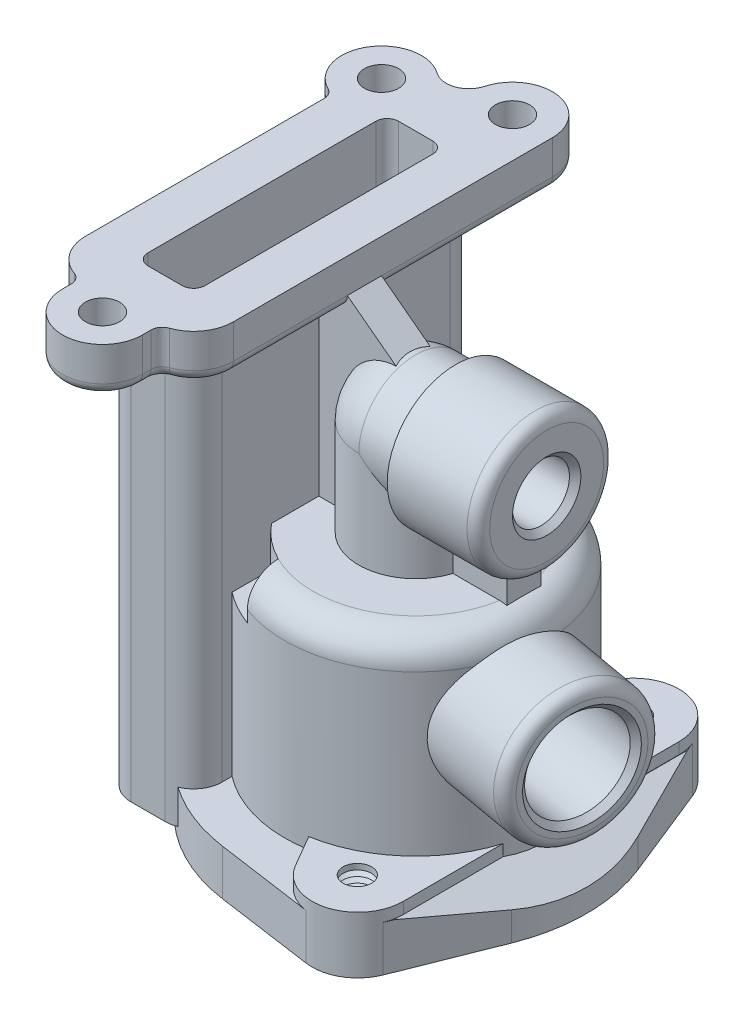
SolidWorks part; units mm, degrees
ref_plane "前基準面" through (0, 0, 0) normal (0, 0, 1) x (1, 0, 0)
ref_plane "上基準面" through (0, 0, 0) normal (0, 1, 0) x (1, 0, 0)
ref_plane "右基準面" through (0, 0, 0) normal (1, 0, 0) x (0, 0, -1)
sketch "草圖1" plane through (0, 0, 0) normal (0, 1, 0) x (1, 0, 0)
  line L0 (-34.2943, 4.8888) -> (-23.6038, 18.5165)
  line L1 (-34.277, -5.0086) -> (-23.539, -18.5989)
  line L2 (21.381, 27.2554) -> (27.8376, 11.1833)
  line L3 (12.8009, 32.1891) -> (-4.3376, 29.6848)
  line L4 (12.9133, -32.1441) -> (-4.2338, -29.6997)
  line L5 (21.4761, -27.1804) -> (27.8766, -11.0859)
  arc A0 (27.8766, -11.0859) -> (27.8376, 11.1833) centre (0, 0) ccw
  arc A1 (-34.2943, 4.8888) -> (-34.277, -5.0086) centre (-28, -0.0489) ccw
  arc A2 (21.381, 27.2554) -> (12.8009, 32.1891) centre (13.9576, 24.2731) ccw
  arc A3 (12.9133, -32.1441) -> (21.4761, -27.1804) centre (14.0424, -24.2242) ccw
  arc A4 (-4.3376, 29.6848) -> (-23.6038, 18.5165) centre (0, 0) ccw
  arc A5 (-23.539, -18.5989) -> (-4.2338, -29.6997) centre (0, 0) ccw
  dimension "D1" = 60
  dimension "D3" = 16
  dimension "D2" = 28
extrude "伸長1" add sketch "草圖1" along normal blind 8
sketch "草圖2" plane through (0, 0, 0) normal (0, 0, 1) x (1, 0, 0)
  line L0 (0, -12.2996) -> (0, 56.8744) construction
  line L1 (10, 60) -> (10, 43)
  line L2 (10, 43) -> (23, 43)
  line L3 (23, 43) -> (23, 0)
  line L4 (12.9133, 0) -> (21.4761, 0) construction
  line L5 (23, 0) -> (0, 0)
  line L6 (0, 0) -> (0, 70)
  arc A0 (10, 60) -> (0, 70) centre (0, 60) ccw
  dimension "D1" = 20
  dimension "D2" = 60
  dimension "D3" = 46
  dimension "D4" = 43
revolve "旋轉1" add sketch "草圖2" angle 360 about L0
sketch "草圖5" plane through (0, 8, 0) normal (0, 1, 0) x (-1, 0, 0)
  line L0 (-21.9576, -24.2731) -> (-22.0424, 24.2242)
  line L1 (-13.9576, -24.2731) -> (0, 0) construction
  line L2 (0, 0) -> (-14.0424, 24.2242) construction
  line L3 (-7.0224, -28.261) -> (9.2376, 0.0161)
  line L4 (9.2376, 0.0161) -> (-7.1212, 28.2363)
  arc A0 (-21.9576, -24.2731) -> (-7.0224, -28.261) centre (-13.9576, -24.2731) ccw
  arc A1 (-7.1212, 28.2363) -> (-22.0423, 24.1962) centre (-14.0424, 24.2242) ccw
  circle M1 centre (0, 0) radius 23
  arc M6 (-12.9133, 32.1441) -> (-21.4761, 27.1804) centre (-14.0424, 24.2242) ccw
  arc M10 (-21.381, -27.2554) -> (-12.8009, -32.1891) centre (-13.9576, -24.2731) ccw
extrude "伸長2" add sketch "草圖5" along normal blind 2 contours L3 L4 L0 M1 | L0 A0 L3 M10 M1 | A1 L0 L4 M6 M1
sketch "草圖6" plane through (0, 0, 0) normal (0, 0, 1) x (1, 0, 0)
  line L0 (22.0117, 8) -> (30, 4)
  line L1 (30, 0) -> (30, 8) construction
  line L2 (30, 4) -> (30, 8)
  line L3 (30, 8) -> (22.0117, 8)
  dimension "D1" = 4
extrude "除料-伸長2" cut sketch "草圖6" against normal through all and the other way through all
sketch "草圖7" plane through (0, 8, 0) normal (0, -1, 0) x (1, 0, 0)
  line L1 (22.0117, 6.6698) -> (22.0117, -6.6698)
  line L2 (22.0117, 6.6698) -> (22.0117, -6.6698)
  arc A1 (22.0117, -6.6698) -> (22.0117, 6.6698) centre (0, 0) ccw
  arc A2 (22.0117, -6.6698) -> (22.0117, 6.6698) centre (0, 0) ccw
  dimension "D1" = 0
extrude "伸長3" add sketch "草圖7" along normal up to next
sketch "草圖8" plane through (0, 0, 0) normal (0, 0, 1) x (1, 0, 0)
  line L0 (0, 60) -> (36.9487, 60) construction
  line L1 (10, 60) -> (-10, 60) construction
  line L2 (0, 60) -> (0, 70)
  line L3 (7, 60) -> (23, 60)
  line L4 (7, 70) -> (7, 72)
  line L5 (7, 72) -> (23, 72)
  line L6 (23, 60) -> (23, 72)
  line L7 (0, 70) -> (7, 70)
  line L8 (0, 60) -> (7, 60)
  arc A0 (10, 60) -> (-10, 60) centre (0, 60) ccw construction
  dimension "D1" = 16
  dimension "D2" = 24
  dimension "D3" = 23
revolve "旋轉2" add sketch "草圖8" angle 360 about L0
ref_plane "平面1" through (0, 28, 0) normal (0, 1, 0) x (-1, 0, 0)
sketch "草圖9" plane through (0, 28, 0) normal (0, 1, 0) x (-1, 0, 0)
  line L0 (0, 0) -> (-48.1518, 0) construction
  line L1 (0, 0) -> (-55.67, 9.8161) construction
  line L2 (-33.3693, 18.069) -> (-35.4531, 6.2513)
  line L3 (-35.4531, 6.2513) -> (0, 0)
  line L4 (0, 0) -> (2.0838, 11.8177)
  line L5 (-33.3693, 18.069) -> (2.0838, 11.8177)
  dimension "D1" = 10
  dimension "D2" = 36
  dimension "D3" = 24
revolve "旋轉3" add sketch "草圖9" angle 360 about L1
ref_plane "平面2" through (0, 82, 0) normal (0, 1, 0) x (-1, 0, 0)
sketch "草圖10" plane through (0, 82, 0) normal (0, 1, 0) x (-1, 0, 0)
  line L1 (25, -25) -> (19, -25)
  line L2 (30, -20) -> (30, 20)
  line L3 (25, 25) -> (19, 25)
  line L4 (14, -20) -> (14, 20)
  arc A0 (25, -25) -> (30, -20) centre (25, -20) ccw
  arc A1 (14, -20) -> (19, -25) centre (19, -20) ccw
  arc A2 (19, 25) -> (14, 20) centre (19, 20) ccw
  arc A3 (30, 20) -> (25, 25) centre (25, 20) ccw
  point P6 (30, -25)
  point P9 (14, -25)
  point P14 (30, 25)
  dimension "D5" = 5
  dimension "D1" = 16
  dimension "D2" = 50
  dimension "D3" = 25
  dimension "D4" = 30
extrude "伸長4" add sketch "草圖10" against normal blind 80
sketch "草圖11" plane through (0, 82, 0) normal (0, 1, 0) x (-1, 0, 0)
  line L0 (22, -25) -> (22, 31.5442) construction
  line L1 (19, -25) -> (25, -25) construction
  line L2 (9, -33) -> (9, 23)
  line L3 (35, -18.9377) -> (35, 23)
  line L4 (15, 33) -> (15, 31.4853)
  line L5 (29, 33) -> (29, 31.4853)
  arc A0 (29, 33) -> (15, 33) centre (22, 33) ccw
  arc A1 (28.9262, -32.6925) -> (36.1111, -20.7294) centre (33, -27) ccw
  arc A2 (9, -33) -> (22.7444, -34.8743) centre (16, -33) ccw
  arc A3 (28.9262, -32.6925) -> (22.7444, -34.8743) centre (26.5984, -35.9453) ccw
  arc A4 (35, 23) -> (30.3333, 29.5997) centre (28, 23) ccw
  arc A5 (13.6667, 29.5997) -> (9, 23) centre (16, 23) ccw
  arc A6 (29, 31.4853) -> (30.3333, 29.5997) centre (31, 31.4853) ccw
  arc A7 (15, 31.4853) -> (13.6667, 29.5997) centre (13, 31.4853) cw
  arc A8 (35, -18.9377) -> (36.1111, -20.7294) centre (37, -18.9377) ccw
  dimension "D1" = 14
  dimension "D2" = 14
  dimension "D3" = 14
  dimension "D9" = 8
  dimension "D12" = 14
  dimension "D13" = 14
  dimension "D11" = 2
  dimension "D14" = 2
  dimension "D4" = 33
  dimension "D5" = 11
  dimension "D6" = 6
  dimension "D7" = 60
  dimension "D8" = 6
  dimension "D10" = 26
extrude "伸長5" add sketch "草圖11" against normal blind 8
sketch "草圖12" plane through (0, 82, 0) normal (0, 1, 0) x (-1, 0, 0)
  line L2 (17, -20) -> (17, 20)
  line L23 (17, 20) -> (17, -20)
  line L24 (19, -22) -> (25, -22)
  line L25 (27, -20) -> (27, 20)
  line L26 (25, 22) -> (19, 22)
  line L28 (19, -22) -> (25, -22)
  line L29 (27, -20) -> (27, 20)
  line L30 (25, 22) -> (19, 22)
  arc A2 (19, 22) -> (17, 20) centre (19, 20) ccw
  arc A3 (19, 22) -> (17, 20) centre (19, 20) ccw
  arc A27 (17, -20) -> (19, -22) centre (19, -20) ccw
  arc A28 (25, -22) -> (27, -20) centre (25, -20) ccw
  arc A29 (27, 20) -> (25, 22) centre (25, 20) ccw
  arc A30 (19, 22) -> (17, 20) centre (19, 20) ccw
  arc A31 (17, -20) -> (19, -22) centre (19, -20) ccw
  arc A32 (25, -22) -> (27, -20) centre (25, -20) ccw
  arc A33 (27, 20) -> (25, 22) centre (25, 20) ccw
  arc A34 (19, 22) -> (17, 20) centre (19, 20) ccw
  dimension "D2" = 3
  dimension "D3" = 3
extrude "除料-伸長3" cut sketch "草圖12" against normal blind 77 contours L29 A33 L30 A3 L2 A31 L28 A32
sketch "草圖15" plane through (0, 0, 0) normal (0, 0, 1) x (1, 0, 0)
  line L0 (-36, 8) -> (-36, 0) construction
  line L1 (-36, 8) -> (-36, 0)
  line L2 (-34.277, 0) -> (-23.539, 0) construction
  line L3 (-28, 10) -> (-28, -3.0026) construction
  line L4 (-36, 0) -> (-28, 0)
  line L5 (-28, 0) -> (-28, 18)
  line L6 (-36, 8) -> (-36, 10)
  arc A0 (-28, 18) -> (-36, 10) centre (-28, 10) ccw
  dimension "D2" = 16
  dimension "D1" = 10
  dimension "D3" = 8
revolve "旋轉4" add sketch "草圖15" angle 360 about L3
sketch "草圖16" plane through (0, 0, 0) normal (0, 0, 1) x (1, 0, 0)
  line L0 (0, -12.0938) -> (0, 81.3353) construction
  line L1 (7, 60) -> (7, 40)
  line L2 (7, 40) -> (20, 40)
  line L3 (20, 40) -> (20, 1)
  line L4 (20, 1) -> (24, 1)
  line L5 (24, 1) -> (24, 0)
  line L6 (12.9133, 0) -> (21.4761, 0) construction
  line L7 (24, 0) -> (0, 0)
  line L8 (0, 0) -> (0, 67)
  arc A0 (7, 60) -> (0, 67) centre (0, 60) ccw
  dimension "D1" = 14
  dimension "D2" = 1
  dimension "D3" = 48
  dimension "D4" = 40
  dimension "D5" = 40
revolve "除料-旋轉2" cut sketch "草圖16" angle 360 about L0
sketch "草圖18" plane through (23, 0, 0) normal (1, 0, 0) x (0, 0, -1)
  circle A0 centre (0, 60) radius 5
  dimension "D1" = 10
extrude "除料-伸長4" cut sketch "草圖18" against normal blind 23
chamfer "導角1" distance 1 angle 45 1 edges at (23, 60, -5)
sketch "草圖19" plane through (35.4531, 0, 6.2513) normal (0.9848, 0, 0.1736) x (0.1736, 0, -0.9848)
  circle A0 centre (0, 28) radius 8
  dimension "D1" = 16
extrude "除料-伸長5" cut sketch "草圖19" against normal blind 36
chamfer "導角2" distance 1 angle 45 1 edges at (36.8423, 28, -1.6271)
sketch "草圖20" plane through (0, 40, 0) normal (0, -1, 0) x (1, 0, 0)
  line L0 (-6, 19.0788) -> (-6, 13.7477)
  line L1 (-6, -13.7477) -> (-6, -19.0788)
  arc A0 (-6, 13.7477) -> (-6, -13.7477) centre (0, 0) ccw
  circle A1 centre (0, 0) radius 20 construction
  arc A2 (-6, 19.0788) -> (-6, -19.0788) centre (0, 0) ccw
  dimension "D1" = 30
  dimension "D2" = 6
extrude "伸長6" add sketch "草圖20" along normal blind 10 and the other way up to surface (3 mm away) other way up to face at (4.5, 43, 0)
sketch "草圖21" plane through (0, 43, 0) normal (0, 1, 0) x (-1, 0, 0)
  line L0 (17, 10.5357) -> (17, -10.5357) construction
  line L1 (17, 10.5357) -> (17, 5.9161)
  line L2 (17, -5.9161) -> (17, -10.5357)
  arc A0 (17, -5.9161) -> (17, 5.9161) centre (0, 0) ccw
  arc A1 (17, -10.5357) -> (17, 10.5357) centre (0, 0) ccw construction
  arc A2 (17, -10.5357) -> (17, 10.5357) centre (0, 0) ccw
  dimension "D1" = 36
extrude "除料-伸長6" cut sketch "草圖21" against normal blind 10
sketch "草圖22" plane through (0, 43, 0) normal (0, 1, 0) x (-1, 0, 0)
  line L0 (14, 18.2483) -> (14, -18.2483) construction
  line L1 (14, 18.2483) -> (14, 11.3137)
  line L2 (8, -21.5639) -> (8, -16.1245)
  line L3 (14, -11.3137) -> (14, -18.2483)
  line L4 (8, 16.1245) -> (8, 21.5639)
  arc A0 (14, 18.2483) -> (14, -18.2483) centre (0, 0) ccw construction
  arc A1 (14, 18.2483) -> (8, 21.5639) centre (0, 0) ccw
  arc A2 (8, -16.1245) -> (14, -11.3137) centre (0, 0) ccw
  arc A3 (8, -21.5639) -> (14, -18.2483) centre (0, 0) ccw
  arc A4 (14, 11.3137) -> (8, 16.1245) centre (0, 0) ccw
  dimension "D1" = 36
  dimension "D2" = 8
extrude "除料-伸長7" cut sketch "草圖22" against normal blind 7
sketch "草圖23" plane through (0, 0, 0) normal (0, 0, 1) x (1, 0, 0)
  line L0 (-9, 76) -> (-1, 69.9499)
  line L1 (-9, 74) -> (-9, 82) construction
  line L2 (-9, 82) -> (-13.6667, 82) construction
  line L3 (0, 70) -> (0, 60) construction
  arc A0 (0, 70) -> (-10, 60) centre (0, 60) ccw construction
  dimension "D1" = 6
  dimension "D2" = 1
rib "肋材1" sketch "草圖23" sketch "草圖23" thickness 6 extrusion direction parallel to sketch draft on no parameters "D1"=6
sketch "草圖24" plane through (0, 0, 0) normal (0, 0, 1) x (1, 0, 0)
  line L0 (19, 48) -> (19, 43)
  line L1 (10, 48) -> (23, 48) construction
  line L2 (23, 43) -> (-8, 43) construction
  line L3 (23, 48) -> (23, 72) construction
  dimension "D1" = 4
rib "肋材2" sketch "草圖24" sketch "草圖24" thickness 6 extrusion direction parallel to sketch draft on no parameters "D1"=6
sketch "草圖25" plane through (0, 82, 0) normal (0, 1, 0) x (-1, 0, 0)
  circle A0 centre (16, -33) radius 3
  circle A1 centre (33, -27) radius 3
  circle A2 centre (22, 33) radius 3
  dimension "D1" = 6
extrude "除料-伸長8" cut sketch "草圖25" against normal through all
sketch "草圖26" plane through (0, 0, 0) normal (0, 0, 1) x (1, 0, 0)
  line L0 (-28, 19.5821) -> (-28, -1.6596) construction
  line L1 (-36, 8) -> (-36, 0) construction
  line L2 (-30.5, 0) -> (-31.366, 0.5)
  line L3 (-34.277, 0) -> (-23.539, 0) construction
  line L4 (-31.366, 0.5) -> (-30.5, 1)
  line L5 (-31.366, 1.5) -> (-30.5, 2)
  line L6 (-30.5, 1) -> (-31.366, 1.5)
  line L7 (-31.366, 2.5) -> (-30.5, 3)
  line L8 (-30.5, 2) -> (-31.366, 2.5)
  line L9 (-31.366, 3.5) -> (-30.5, 4)
  line L10 (-30.5, 3) -> (-31.366, 3.5)
  line L11 (-31.366, 4.5) -> (-30.5, 5)
  line L12 (-30.5, 4) -> (-31.366, 4.5)
  line L13 (-31.366, 5.5) -> (-30.5, 6)
  line L14 (-30.5, 5) -> (-31.366, 5.5)
  line L15 (-31.366, 6.5) -> (-30.5, 7)
  line L16 (-30.5, 6) -> (-31.366, 6.5)
  line L17 (-31.366, 7.5) -> (-30.5, 8)
  line L18 (-30.5, 7) -> (-31.366, 7.5)
  line L19 (-31.366, 8.5) -> (-30.5, 9)
  line L20 (-30.5, 8) -> (-31.366, 8.5)
  line L21 (-30.5, 9) -> (-30.5, 12)
  line L22 (-30.5, 12) -> (-28, 13.4434)
  line L23 (-28, 13.4434) -> (-28, 0)
  line L24 (-28, 0) -> (-30.5, 0)
  dimension "D1" = 8
  dimension "D2" = 60
  dimension "D3" = 0.5
  dimension "D4" = 1
  dimension "D5" = 5
  dimension "D6" = 12
  dimension "D7" = 60
revolve "除料-旋轉3" cut sketch "草圖26" angle 360 about L0
pattern_circular "環狀複製排列1" count 3 over 360 about axis through (0, 0, 0) along (0, 1, 0) of "除料-旋轉3"
fillet "圓角1" radius 2 1 edges at (23, 60, 12)
fillet "圓角2" radius 2 1 edges at (33.3693, 28, 18.069)
fillet "圓角10" radius 5 5 edges at (21.4315, 29.1695, -8.3482) (-8, 43, 18.8442) (23, 43, 0) (-8, 43, -18.8442) (19, 43, 0)
fillet "圓角11" radius 2 14 edges at (-9, 74, -18) (-15.0542, 74, -39.9358) (-25.2671, 74, -32.1734) (-39.0009, 74, -30.6041) (-35.3003, 74, -19.9918) (-35, 74, 2.0311) (-33.7155, 74, 27.0415) (-29.367, 74, 30.3306) (-29, 74, 32.2426) (-9, 74, 13) (-10.2845, 74, 27.0415) (-14.633, 74, 30.3306) (-15, 74, 32.2426) (-22, 74, 40)
